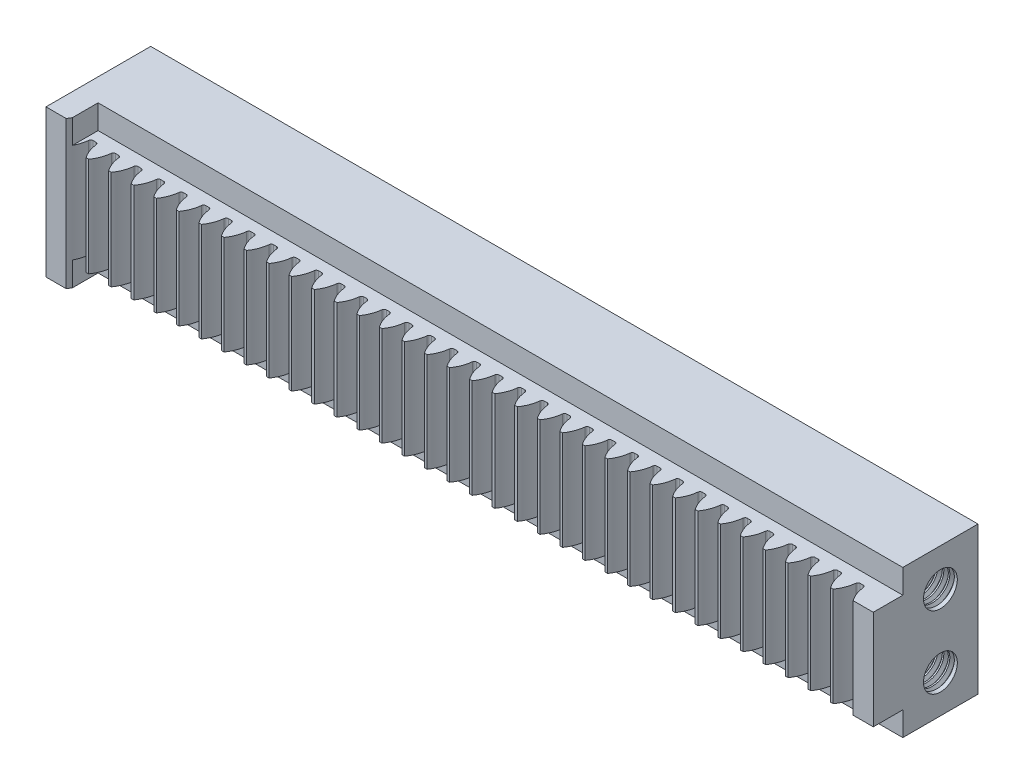
SolidWorks part; units mm, degrees
ref_plane "Ebene vorne" through (0, 0, 0) normal (0, 0, 1) x (1, 0, 0)
ref_plane "Ebene oben" through (0, 0, 0) normal (0, 1, 0) x (1, 0, 0)
ref_plane "Ebene rechts" through (0, 0, 0) normal (1, 0, 0) x (0, 0, -1)
sketch "Skizze8" plane through (0, 0, 0) normal (0, 1, 0) x (1, 0, 0)
  line L1 (0, 0) -> (110, 0)
  line L2 (0, 0) -> (0, 13.925)
  line L3 (0, 13.925) -> (110, 13.925)
  line L4 (110, 0) -> (110, 13.925)
  dimension "D1" = 13.925
  dimension "D2" = 110
extrude "Aufsatz-Linear austragen3" add sketch "Skizze8" along normal blind 19.6
sketch "Skizze9" plane through (0, 0, 0) normal (0, -1, 0) x (1, 0, 0)
  line L0 (10, -21.7) -> (10, 0.153) construction
  line L1 (9.7979, -2.45) -> (10.2021, -2.45)
  line L2 (0, -13.925) -> (0, 0) construction
  line L3 (0, 0) -> (110, 0) construction
  arc A0 (10.5005, -2.1811) -> (12.0608, 0.8022) centre (15.0359, -2.6535) cw
  arc A1 (9.4995, -2.1811) -> (7.9392, 0.8022) centre (4.9641, -2.6535) ccw
  arc A2 (7.9392, 0.8022) -> (12.0608, 0.8022) centre (10, -17.0794) cw
  arc A3 (10.2021, -2.45) -> (10.5005, -2.1811) centre (10.2021, -2.15) ccw
  arc A4 (9.4995, -2.1811) -> (9.7979, -2.45) centre (9.7979, -2.15) ccw
  point P9 (10, -2.45)
  dimension "D1" = 4.56
  dimension "D2" = 18
  dimension "D3" = 0.3
  dimension "D4" = 19.25
  dimension "D5" = 10
  dimension "D6" = 21.7
extrude "Schnitt-Linear austragen1" cut sketch "Skizze9" against normal blind 19.7
pattern_linear "Lineares Muster1" count 33 spacing 3 along (1, 0, 0) of "Schnitt-Linear austragen1"
pattern_linear "Lineares Muster2" count 3 spacing 3 along (-1, 0, 0) of "Schnitt-Linear austragen1"
sketch "Skizze10" plane through (110, 0, 0) normal (1, 0, 0) x (0, 0, -1)
  line L0 (13.925, 19.6) -> (13.925, 0) construction
  line L2 (0, 0) -> (13.925, 0) construction
  circle A0 centre (8.925, 14.6) radius 2.25
  circle A1 centre (8.925, 5) radius 2.25
  dimension "D1" = 4.5
  dimension "D2" = 4.5
  dimension "D3" = 5
  dimension "D4" = 5
  dimension "D5" = 9.6
  dimension "D6" = 5
extrude "Schnitt-Linear austragen2" cut sketch "Skizze10" against normal blind 12
sketch "Skizze11" plane through (110, 0, 0) normal (1, 0, 0) x (0, 0, -1)
  line L0 (13.925, 19.6) -> (13.925, 0) construction
  line L1 (0, 19.6) -> (3.925, 19.6)
  line L2 (0, 19.6) -> (0, 16.4)
  line L3 (0, 16.4) -> (3.925, 16.4)
  line L4 (3.925, 19.6) -> (3.925, 16.4)
  line L5 (0, 0) -> (3.925, 0)
  line L6 (0, 0) -> (0, 3.2)
  line L7 (0, 3.2) -> (3.925, 3.2)
  line L8 (3.925, 0) -> (3.925, 3.2)
  dimension "D1" = 3.2
  dimension "D2" = 3.2
  dimension "D3" = 10
  dimension "D4" = 10
extrude "Schnitt-Linear austragen3" cut sketch "Skizze11" against normal blind 107
thread "Gewinde1" pitch 0.8 method cut profile "Gewindeprofil1" start angle 0, offset 0, length 12, pitch 0.8, diameter 4.5
ref_plane "Ebene1" through (110, 5, -6.675) normal (0, -1, 0) x (0, 0, 1)
sketch "Gewindeprofil1" plane through (110, 5, -6.675) normal (0, -1, 0) x (0, 0, 1)
  line L0 (0, 0) -> (0, 0.8) construction
  line L1 (0, 0) -> (0.433, 0.25)
  line L2 (0.433, 0.25) -> (0.433, 0.35)
  line L3 (0.433, 0.35) -> (0, 0.6)
  line L4 (0.433, 0.3) -> (0, 0.3) construction
  line L11 (0, 0) -> (0, 0.6)
  point P2 (0, 0)
  dimension "Pitch" = 0.8
  dimension "Profile_Angle" = 60
  dimension "Profile_Land" = 0.1
  dimension "Profile_Height" = 0.433
thread "Gewinde2" pitch 0.8 method cut profile "Gewindeprofil2" start angle 0, offset 0, length 12, pitch 0.8, diameter 4.5
ref_plane "Ebene2" through (110, 14.6, -6.675) normal (0, -1, 0) x (0, 0, 1)
sketch "Gewindeprofil2" plane through (110, 14.6, -6.675) normal (0, -1, 0) x (0, 0, 1)
  line L0 (0, 0) -> (0, 0.8) construction
  line L1 (0, 0) -> (0.433, 0.25)
  line L2 (0.433, 0.25) -> (0.433, 0.35)
  line L3 (0.433, 0.35) -> (0, 0.6)
  line L4 (0.433, 0.3) -> (0, 0.3) construction
  line L11 (0, 0) -> (0, 0.6)
  point P2 (0, 0)
  dimension "Pitch" = 0.8
  dimension "Profile_Angle" = 60
  dimension "Profile_Land" = 0.1
  dimension "Profile_Height" = 0.433
